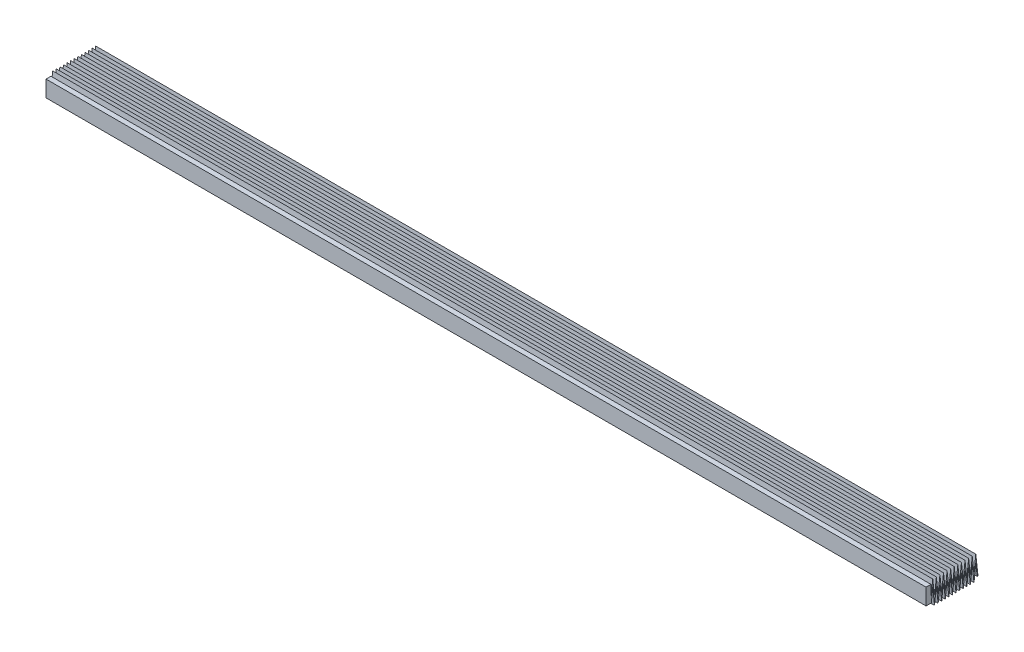
SolidWorks part; units mm, degrees
ref_plane "Front Plane" through (0, 0, 0) normal (0, 0, 1) x (1, 0, 0)
ref_plane "Top Plane" through (0, 0, 0) normal (0, 1, 0) x (1, 0, 0)
ref_plane "Right Plane" through (0, 0, 0) normal (1, 0, 0) x (0, 0, -1)
sketch "Sketch2" plane through (0, 0, 0) normal (0, 0, 1) x (1, 0, 0)
  line L1 (-270, 10) -> (270, 10)
  line L2 (-270, 10) -> (-270, 0)
  line L3 (-270, 0) -> (270, 0)
  line L4 (270, 10) -> (270, 0)
  point P4 (0, 0)
  dimension "D1" = 10
  dimension "D2" = 540
extrude "Boss-Extrude1" add sketch "Sketch2" along normal blind 3
sketch "Sketch3" plane through (270, 0, 0) normal (1, 0, 0) x (0, 0, -1)
  line L0 (0, 10) -> (28.6258, 10) construction
  line L1 (0, 0) -> (28.6258, 0) construction
  line L3 (0, 0) -> (1.101, 10)
  line L4 (1.101, 10) -> (2.202, 0)
  line L5 (2.202, 0) -> (3.303, 10)
  line L6 (3.303, 10) -> (4.404, 0)
  line L7 (4.404, 0) -> (5.505, 10)
  line L8 (5.505, 10) -> (6.606, 0)
  line L9 (6.606, 0) -> (7.7069, 10)
  line L10 (7.7069, 10) -> (8.8079, 0)
  line L11 (8.8079, 0) -> (9.9089, 10)
  line L12 (9.9089, 10) -> (11.0099, 0)
  line L13 (11.0099, 0) -> (12.1109, 10)
  line L14 (12.1109, 10) -> (13.2119, 0)
  line L15 (13.2119, 0) -> (14.3129, 10)
  line L16 (14.3129, 10) -> (15.4139, 0)
  line L17 (15.4139, 0) -> (16.5149, 10)
  line L18 (16.5149, 10) -> (17.6159, 0)
  line L20 (17.6159, 0) -> (18.7169, 10)
  line L21 (18.7169, 10) -> (19.8179, 0)
  line L22 (19.8179, 0) -> (20.9189, 10)
  line L23 (20.9189, 10) -> (22.0199, 0)
  line L24 (22.0199, 0) -> (23.1208, 10)
  line L25 (23.1208, 10) -> (24.2218, 0)
  line L26 (24.2218, 0) -> (25.3228, 10)
  line L27 (25.3228, 10) -> (26.4238, 0)
  line L28 (26.4238, 0) -> (27.5248, 10)
  line L29 (27.5248, 10) -> (28.6258, 0)
  line L30 (28.6258, 10) -> (28.6258, 0) construction
  line L32 (28.6258, 10) -> (28.6258, 0) construction
  point P1 (0, 0)
  point P8 (0, 0)
  point P24 (0, 0)
  point P25 (0, 0)
extrude "Extrude-Thin1" add sketch "Sketch3" against normal through all thin thin type mid plane wall 0.5
